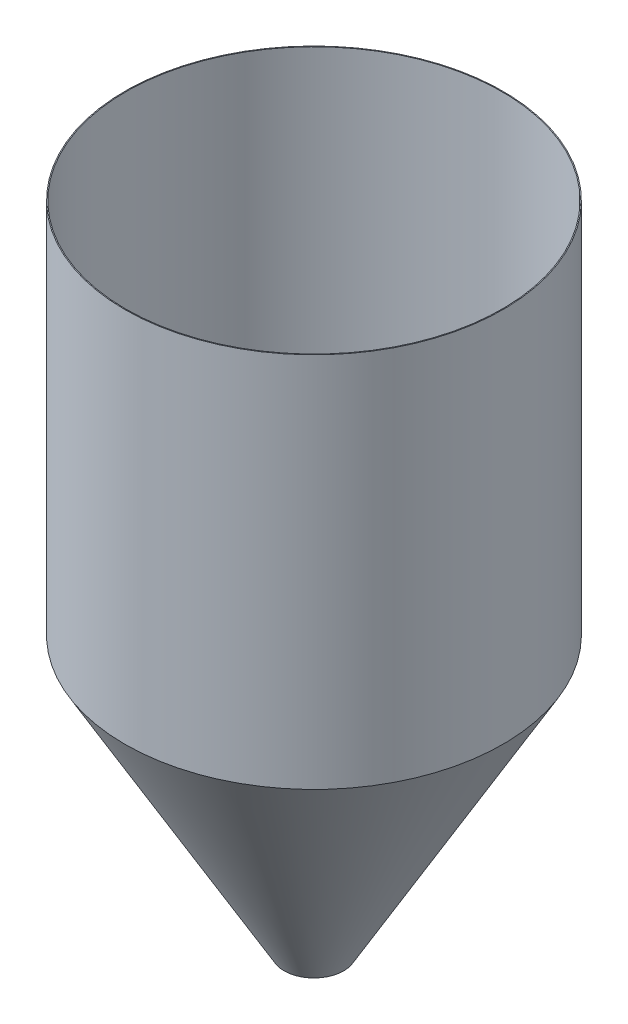
SolidWorks part; units mm, degrees
material "5052-H36"
ref_plane "Front Plane" through (0, 0, 0) normal (0, 0, 1) x (1, 0, 0)
ref_plane "Top Plane" through (0, 0, 0) normal (0, 1, 0) x (1, 0, 0)
ref_plane "Right Plane" through (0, 0, 0) normal (1, 0, 0) x (0, 0, -1)
sketch "Sketch1" plane through (0, 0, 0) normal (0, 1, 0) x (1, 0, 0)
  circle A0 centre (0, 0) radius 254
  circle A1 centre (0, 0) radius 255.2141
  dimension "D1" = 508
  dimension "D2" = 1.2141
extrude "Boss-Extrude1" add sketch "Sketch1" along normal blind 508
sketch "Sketch2" plane through (0, 0, 0) normal (0, 0, 1) x (1, 0, 0)
  line L0 (254, 0) -> (38.989, -372.41)
  line L1 (254, 0) -> (0, -439.9409) construction
  line L2 (0, -439.9409) -> (0, 0) construction
  line L3 (254, 0) -> (-254, 0) construction
  line L4 (38.989, -372.41) -> (40.2031, -372.41)
  line L5 (40.2031, -372.41) -> (255.2141, 0)
  line L6 (255.2141, 0) -> (254, 0)
  line L7 (254, 0) -> (254, 508) construction
  dimension "D1" = 77.978
  dimension "D2" = 508
  dimension "D3" = 508
revolve "Revolve1" add sketch "Sketch2" angle 360 about L2
equation "\"D3@Sketch2\"=\"D2@Sketch2\""
